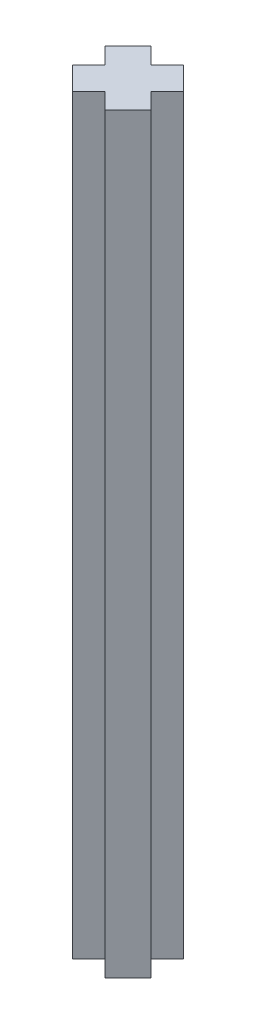
SolidWorks part; units mm, degrees
ref_plane "Front Plane" through (0, 0, 0) normal (0, 0, 1) x (1, 0, 0)
ref_plane "Top Plane" through (0, 0, 0) normal (0, 1, 0) x (1, 0, 0)
ref_plane "Right Plane" through (0, 0, 0) normal (1, 0, 0) x (0, 0, -1)
sketch "Sketch1" plane through (0, 0, 0) normal (0, 1, 0) x (1, 0, 0)
  line L0 (-0.627, 2.9162) -> (-2.423, 4.7122)
  line L1 (-3.167, -2.1638) -> (1.913, -2.1638) construction
  line L2 (-3.167, -2.1638) -> (-3.167, 2.9162) construction
  line L3 (-3.167, 2.9162) -> (1.913, 2.9162) construction
  line L4 (1.913, -2.1638) -> (1.913, 2.9162) construction
  line L5 (-3.167, -2.1638) -> (1.913, 2.9162) construction
  line L6 (-3.167, 2.9162) -> (1.913, -2.1638) construction
  line L7 (-3.167, 0.3762) -> (-4.963, 2.1722)
  line L8 (-4.963, 2.1722) -> (-2.423, 4.7122)
  line L9 (1.913, 0.3762) -> (3.7091, -1.4199)
  line L10 (-0.627, -2.1638) -> (1.1691, -3.9599)
  line L11 (1.1691, -3.9599) -> (3.7091, -1.4199)
  line L12 (-3.167, 0.3762) -> (-4.963, -1.4199)
  line L13 (-0.627, -2.1638) -> (-2.423, -3.9599)
  line L14 (-4.963, -1.4199) -> (-2.423, -3.9599)
  line L15 (1.913, 0.3762) -> (3.7091, 2.1722)
  line L16 (1.1691, 4.7122) -> (3.7091, 2.1722)
  line L17 (-0.627, 2.9162) -> (1.1691, 4.7122)
  point P0 (-0.627, 0.3762)
  dimension "D1" = 2.54
  dimension "D2" = 5.08
  dimension "D3" = 5.08
  dimension "D4" = 8.6721
  dimension "D5" = 3.5921
  dimension "D6" = 3.5921
  dimension "D7" = 3.5921
  dimension "D8" = 3.5921
  dimension "D9" = 8.6721
  dimension "D10" = 0
  dimension "D11" = 3.5921
  dimension "D12" = 5.08
  dimension "D13" = 2.54
  dimension "D14" = 2.54
  dimension "D15" = 2.54
  dimension "D16" = 2.54
  dimension "D17" = 2.54
  dimension "D18" = 2.54
  dimension "D19" = 2.54
  dimension "D20" = 2.54
extrude "Boss-Extrude1" add sketch "Sketch1" along normal blind 82.8261
scale "Scale1" scale about centroid uniform scaling yes scale factor 0.92
